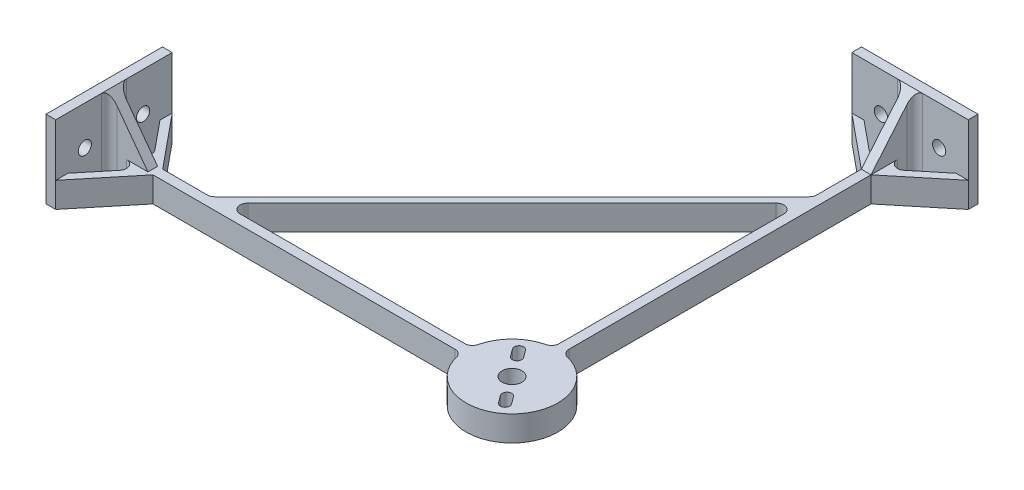
SolidWorks part; units mm, degrees
material "ABS"
ref_plane "Front Plane" through (0, 0, 0) normal (0, 0, 1) x (1, 0, 0)
ref_plane "Top Plane" through (0, 0, 0) normal (0, 1, 0) x (1, 0, 0)
ref_plane "Right Plane" through (0, 0, 0) normal (1, 0, 0) x (0, 0, -1)
sketch "Sketch1" plane through (0, 0, 0) normal (0, 1, 0) x (1, 0, 0)
  line L0 (-1.5875, 14.9158) -> (-1.5875, 130.175)
  line L1 (1.5875, 130.175) -> (1.5875, 14.9158)
  line L2 (-1.5875, 130.175) -> (1.5875, 130.175)
  line L4 (-14.9158, -1.5875) -> (-130.175, -1.5875)
  line L5 (-130.175, -1.5875) -> (-130.175, 1.5875)
  line L8 (-130.175, 1.5875) -> (-14.9158, 1.5875)
  line L9 (0, 0) -> (-130.175, 0) construction
  line L11 (0, 0) -> (0, 146.05) construction
  circle A0 centre (0, 0) radius 15
  point P19 (0, 0)
  point P21 (0, 0)
  dimension "D1" = 30
  dimension "D2" = 3.175
  dimension "D4" = 1.5875
  dimension "D3" = 2
  dimension "D5" = 130.175
extrude "Boss-Extrude2" add sketch "Sketch1" along normal blind 8.255 contours A0
extrude "Boss-Extrude3" add sketch "Sketch1<6>" along normal blind 8.255 contours L4 A0 | A0 | A0 region at (0, 0, -72.5735) region at (-72.5735, 0, 0)
sketch "Sketch1<6>" plane through (0, 0, 0) normal (0, 1, 0) x (1, 0, 0) same geometry as "Sketch1"
sketch "Sketch5" plane through (0, 8.255, 0) normal (0, 1, 0) x (1, 0, 0)
  line L0 (0, 0) -> (130.175, 0) construction
  line L1 (0, 0) -> (0, -22.3627) construction
  line L2 (-6.4967, 8.7797) -> (0, 0) construction
  line L3 (-4.6836, 6.3296) -> (-6.4967, 8.7797) construction
  line L4 (-5.9087, 5.4231) -> (-7.7217, 7.8732)
  line L5 (-3.4586, 7.2361) -> (-5.2716, 9.6862)
  line L6 (0, 0) -> (1.0099, 0.7473) construction
  line L7 (4.6836, -6.3296) -> (6.4967, -8.7797) construction
  line L8 (3.4586, -7.2361) -> (5.2716, -9.6862)
  line L9 (5.9087, -5.4231) -> (7.7217, -7.8732)
  line L10 (-1.5875, 130.175) -> (1.5875, 130.175) construction
  arc A0 (3.4586, -7.2361) -> (5.9087, -5.4231) centre (4.6836, -6.3296) cw
  arc A1 (-5.9087, 5.4231) -> (-3.4586, 7.2361) centre (-4.6836, 6.3296) ccw
  arc A2 (-5.2716, 9.6862) -> (-7.7217, 7.8732) centre (-6.4967, 8.7797) ccw
  arc A3 (7.7217, -7.8732) -> (5.2716, -9.6862) centre (6.4967, -8.7797) cw
  circle A6 centre (0, 0) radius 3.25
  point P8 (-5.5901, 7.5546)
  point P17 (5.5901, -7.5546)
  point P18 (0, 0)
  dimension "D3" = 3.048
  dimension "D5" = 6.5
  dimension "D1" = 7.874
  dimension "D2" = 3.048
  dimension "D4" = 53.5
extrude "Cut-Extrude3" cut sketch "Sketch5" against normal blind 63.5
ref_axis "Axis1" through (0, 0, 0) along (0, 1, 0)
ref_plane "Plane1" through (0, 0, 0) normal (0, 0, 1) x (1, 0, 0)
ref_plane "Plane2" through (0, 0, 0) normal (1, 0, 0) x (0, 0, -1)
sketch "Sketch7" plane through (0, 0, 0) normal (1, 0, 0) x (0, 0, -1)
  line L1 (130.175, 0) -> (133.35, 0)
  line L2 (130.175, 0) -> (130.175, 25.4)
  line L3 (130.175, 25.4) -> (133.35, 25.4)
  line L4 (133.35, 0) -> (133.35, 25.4)
  dimension "D1" = 3.175
  dimension "D2" = 25.4
extrude "Boss-Extrude5" add sketch "Sketch7" along normal blind 19.05 and the other way blind 19.05
sketch "Sketch8" plane through (-19.05, 0, 0) normal (-1, 0, 0) x (0, 0, 1)
  line L1 (-133.35, 0) -> (-130.175, 0)
  line L2 (-133.35, 0) -> (-133.35, 25.4)
  line L3 (-133.35, 25.4) -> (-130.175, 25.4)
  line L4 (-130.175, 0) -> (-130.175, 25.4)
sketch "Sketch12" plane through (0, 0, -133.35) normal (0, 0, -1) x (-1, 0, 0)
  line L0 (-19.05, 12.7) -> (19.05, 12.7) construction
  line L1 (-19.05, 0) -> (-19.05, 25.4) construction
  line L2 (19.05, 0) -> (19.05, 25.4) construction
  line L9 (0, 12.7) -> (0, 25.4) construction
  line L10 (19.05, 25.4) -> (-19.05, 25.4) construction
  circle A0 centre (9.525, 12.7) radius 2.159
  circle A1 centre (-9.525, 12.7) radius 2.159
extrude "Cut-Extrude6" cut sketch "Sketch12" against normal through all
pattern_circular "CirPattern2" count 2 every 90 about axis through (0, 0, 0) along (0, 1, 0) of "Boss-Extrude5"
pattern_circular "CirPattern3" count 2 every 90 about axis through (0, 0, 0) along (0, 1, 0) of "Cut-Extrude6"
sketch "Sketch13" plane through (0, 0, 0) normal (0, -1, 0) x (1, 0, 0)
  line L0 (-96.6289, -1.5875) -> (-1.5875, -96.6289)
  line L1 (-130.175, -1.5875) -> (-14.9158, -1.5875) construction
  line L2 (-1.5875, -14.9158) -> (-1.5875, -130.175) construction
  line L3 (-100.2211, -1.5875) -> (-1.5875, -100.2211)
  line L4 (-96.6289, -1.5875) -> (-100.2211, -1.5875)
  line L5 (-1.5875, -100.2211) -> (-1.5875, -96.6289)
  line L6 (-19.05, -130.175) -> (-1.5875, -130.175) construction
  line L7 (-130.175, -1.5875) -> (-130.175, -19.05) construction
  line L8 (-19.05, -130.175) -> (-1.5875, -115.8315)
  line L9 (-1.5875, -115.8315) -> (-1.5875, -119.1185)
  line L10 (-1.5875, -119.1185) -> (-15.0482, -130.175)
  line L11 (-15.0482, -130.175) -> (-19.05, -130.175)
  line L12 (19.05, -130.175) -> (1.5875, -115.8315)
  line L13 (1.5875, -130.175) -> (1.5875, -14.9158) construction
  line L14 (1.5875, -115.8315) -> (1.5875, -119.1185)
  line L15 (1.5875, -119.1185) -> (15.0482, -130.175)
  line L16 (1.5875, -130.175) -> (19.05, -130.175) construction
  line L17 (15.0482, -130.175) -> (19.05, -130.175)
  line L18 (-119.1185, 1.5875) -> (-130.175, 15.0482)
  line L19 (-130.175, 19.05) -> (-115.8315, 1.5875)
  line L20 (-130.175, 15.0482) -> (-130.175, 19.05)
  line L21 (-119.1185, -1.5875) -> (-130.175, -15.0482)
  line L22 (-130.175, -19.05) -> (-115.8315, -1.5875)
  line L23 (-115.8315, -1.5875) -> (-119.1185, -1.5875)
  line L24 (-115.8315, 1.5875) -> (-119.1185, 1.5875)
  line L25 (-130.175, -15.0482) -> (-130.175, -19.05)
  point P8 (-1.5875, -72.5454)
  point P9 (-1.5875, -98.425)
  point P12 (-98.425, -1.5875)
  point P25 (-1.5875, -117.475)
  point P30 (1.5875, -117.475)
  point P42 (0, 0)
  dimension "D1" = 31.75
  dimension "D2" = 31.75
  dimension "D3" = 2.54
  dimension "D4" = 2.54
  dimension "D5" = 2.54
  dimension "D6" = 12.7
  dimension "D7" = 2
extrude "Boss-Extrude6" add sketch "Sketch13" against normal up to surface (8.255 mm away) up to face at (0, 8.255, 3.25)
sketch "Sketch14" plane through (0, 0, 0) normal (0, 0, 1) x (1, 0, 0)
  line L0 (-130.175, 25.4) -> (-117.475, 8.255)
  line L1 (-14.9158, 8.255) -> (-115.8315, 8.255) construction
  line L2 (-117.475, 8.255) -> (-130.175, 8.255)
  line L3 (-130.175, 8.255) -> (-130.175, 25.4)
  dimension "D1" = 12.7
extrude "Boss-Extrude7" add sketch "Sketch14" along normal up to surface and the other way up to surface up to face at (-124.6467, 4.1275, 1.5875) other way up to face at (-124.6467, 4.1275, -1.5875)
sketch "Sketch15" plane through (0, 0, 0) normal (1, 0, 0) x (0, 0, -1)
  line L0 (130.175, 25.4) -> (115.8315, 8.255)
  line L1 (115.8315, 8.255) -> (115.8315, 0) construction
  line L2 (130.175, 8.255) -> (115.8315, 8.255) construction
  line L3 (115.8315, 8.255) -> (130.175, 8.255)
  line L4 (130.175, 8.255) -> (130.175, 25.4)
extrude "Boss-Extrude8" add sketch "Sketch15" along normal up to surface and the other way up to surface up to face at (1.5875, 4.1275, -65.3736) other way up to face at (-1.5875, 4.1275, -108.0263)
fillet "Fillet1" radius 2.54 16 edges at (-130.175, 12.7, 1.5875) (-130.175, 12.7, -1.5875) (-119.1185, 4.1275, -1.5875) (-119.1185, 4.1275, 1.5875) (1.5875, 12.7, -130.175) (-1.5875, 12.7, -130.175) (-1.5875, 4.1275, -119.1185) (1.5875, 4.1275, -119.1185) (-1.5875, 4.1275, -96.6289) (-96.6289, 4.1275, -1.5875) (-100.2211, 4.1275, -1.5875) (-1.5875, 4.1275, -100.2211) (-14.9158, 4.1275, -1.5875) (-14.9158, 4.1275, 1.5875) (1.5875, 4.1275, -14.9158) (-1.5875, 4.1275, -14.9158)
